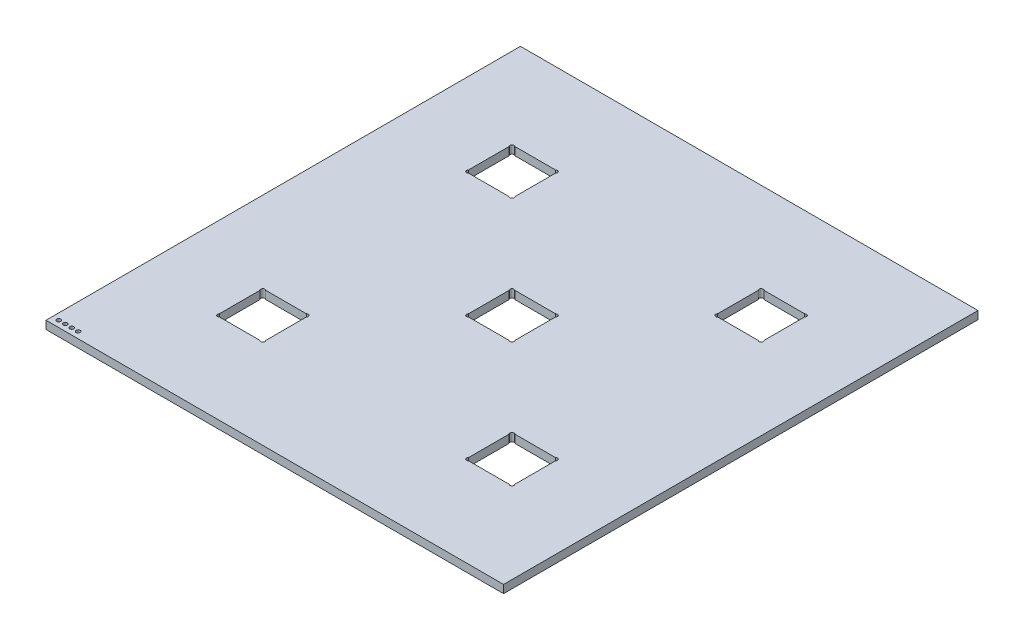
SolidWorks part; units mm, degrees
ref_plane "Front" through (0, 0, 0) normal (0, 0, 1) x (1, 0, 0)
ref_plane "Top" through (0, 0, 0) normal (0, 1, 0) x (1, 0, 0)
ref_plane "Right" through (0, 0, 0) normal (1, 0, 0) x (0, 0, -1)
sketch "Sketch1" plane through (0, 0, 0) normal (0, 1, 0) x (1, 0, 0)
  line L1 (-90.3859, -93.726) -> (90.3859, -93.726)
  line L2 (-90.3859, -93.726) -> (-90.3859, 93.726)
  line L3 (-90.3859, 93.726) -> (90.3859, 93.726)
  line L4 (90.3859, -93.726) -> (90.3859, 93.726)
  line L5 (-90.3859, -93.726) -> (90.3859, 93.726) construction
  line L6 (-90.3859, 93.726) -> (90.3859, -93.726) construction
  point P0 (0, 0)
  dimension "D1" = 180.7718
  dimension "D2" = 187.452
extrude "Boss-Extrude1" add sketch "Sketch1" along normal blind 3.175
sketch "Sketch2" plane through (0, 3.175, 0) normal (0, 1, 0) x (1, 0, 0)
  line L0 (-90.3859, 93.726) -> (90.3859, -93.726) construction
  line L2 (-9.144, -9.144) -> (9.144, -9.144)
  line L3 (-9.144, -9.144) -> (-9.144, 9.144)
  line L4 (-9.144, 9.144) -> (9.144, 9.144)
  line L5 (9.144, -9.144) -> (9.144, 9.144)
  line L6 (-9.144, -9.144) -> (9.144, 9.144) construction
  line L7 (-9.144, 9.144) -> (9.144, -9.144) construction
  point P4 (0, 0)
  point P10 (0, 0)
  dimension "D1" = 18.288
  dimension "D2" = 18.288
extrude "Cut-Extrude1" cut sketch "Sketch2" against normal blind 3.175
sketch "Sketch3" plane through (0, 3.175, 0) normal (0, 1, 0) x (1, 0, 0)
  line L0 (9.144, -9.144) -> (8.0215, -9.144) construction
  line L6 (-9.144, -9.144) -> (9.144, -9.144) construction
  line L7 (9.144, -9.144) -> (9.144, -8.0215) construction
  line L8 (9.144, -9.144) -> (9.144, 9.144) construction
  line L9 (9.144, 0) -> (-9.144, 0) construction
  line L10 (-9.144, 9.144) -> (-9.144, -9.144) construction
  line L11 (0, -9.144) -> (0, 9.144) construction
  line L12 (9.144, 9.144) -> (-9.144, 9.144) construction
  circle A4 centre (8.5827, -8.5827) radius 0.7937
  circle A5 centre (-8.5827, -8.5827) radius 0.7937
  circle A6 centre (-8.5827, 8.5827) radius 0.7937
  circle A7 centre (8.5827, 8.5827) radius 0.7937
  dimension "D1" = 1.5875
extrude "Cut-Extrude2" cut sketch "Sketch3" against normal through all
sketch "Sketch8" plane through (0, 3.175, 0) normal (0, 1, 0) x (1, 0, 0)
  line L0 (90.3859, -93.726) -> (-90.3859, 93.726) construction
  line L2 (49.2125, 49.2125) -> (-49.2125, 49.2125) construction
  line L3 (49.2125, 49.2125) -> (49.2125, -49.2125) construction
  line L4 (49.2125, -49.2125) -> (-49.2125, -49.2125) construction
  line L5 (-49.2125, 49.2125) -> (-49.2125, -49.2125) construction
  line L6 (49.2125, 49.2125) -> (-49.2125, -49.2125) construction
  line L7 (49.2125, -49.2125) -> (-49.2125, 49.2125) construction
  point P4 (0, 0)
  point P11 (-49.2125, -49.2125)
  point P12 (-49.2125, 49.2125)
  point P13 (49.2125, 49.2125)
  point P14 (49.2125, -49.2125)
  dimension "D1" = 98.425
pattern_sketch "Sketch-Pattern1" of "Cut-Extrude1", "Cut-Extrude2" driven by "Sketch8"
sketch "Sketch4" plane through (0, 3.175, 0) normal (0, 1, 0) x (1, 0, 0)
  line L0 (-87.8459, -91.186) -> (90.3859, -91.186) construction
  line L1 (-90.3859, -93.726) -> (-87.8459, -93.726) construction
  line L2 (-90.3859, -93.726) -> (-90.3859, -91.186) construction
  line L3 (-90.3859, -91.186) -> (-87.8459, -91.186) construction
  line L4 (-87.8459, -93.726) -> (-87.8459, -91.186) construction
  line L5 (90.3859, -93.726) -> (90.3859, 93.726) construction
  text T0 "TR_BIT" font "Consolas" height 3.175
  dimension "D1" = 2.54
extrude "Cut-Extrude3" [suppressed] cut sketch "Sketch4" against normal blind 1.5875
sketch "Sketch9" plane through (0, 3.175, 0) normal (0, 1, 0) x (1, 0, 0)
  line L0 (-90.3859, 93.726) -> (-90.3859, -93.726) construction
  line L1 (-90.3859, -93.726) -> (90.3859, -93.726) construction
  circle A0 centre (-87.8459, -91.186) radius 0.7937
  dimension "D1" = 1.5875
  dimension "D2" = 2.54
  dimension "D3" = 2.54
extrude "Cut-Extrude4" cut sketch "Sketch9" against normal blind 1.27
pattern_linear "LPattern1" count 4 spacing 2.54 along (1, 0, 0) of "Cut-Extrude4"
